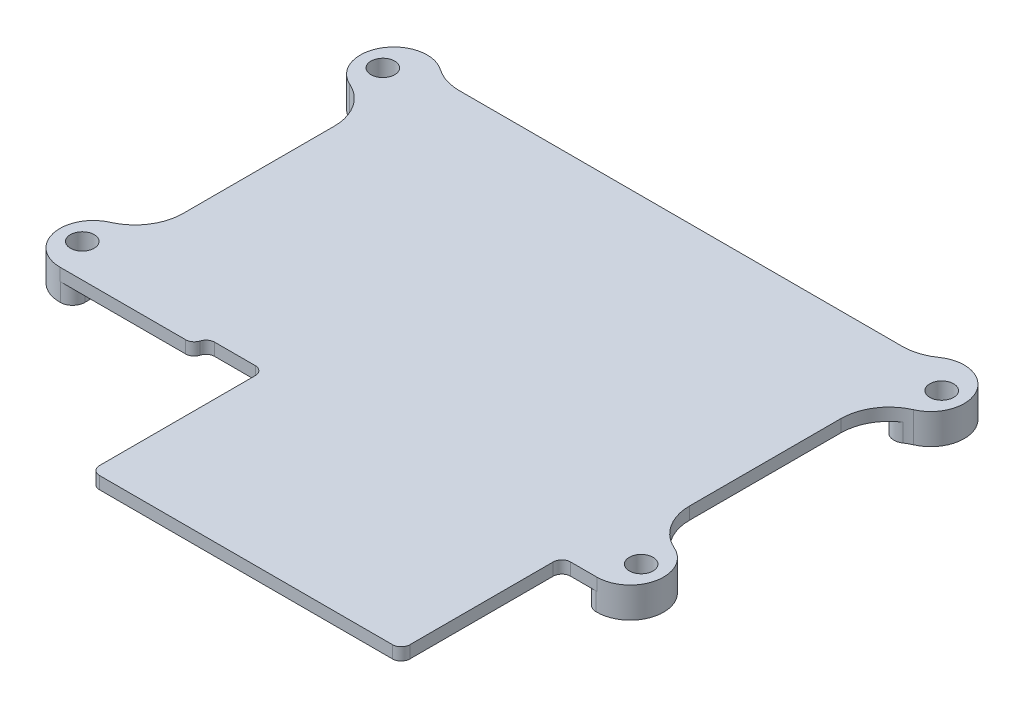
SolidWorks part; units mm, degrees
ref_plane "Front Plane" through (0, 0, 0) normal (0, 0, 1) x (1, 0, 0)
ref_plane "Top Plane" through (0, 0, 0) normal (0, 1, 0) x (1, 0, 0)
ref_plane "Right Plane" through (0, 0, 0) normal (1, 0, 0) x (0, 0, -1)
sketch "Sketch1" plane through (0, 0, 0) normal (0, 1, 0) x (1, 0, 0)
  line L0 (26.2382, 18.5875) -> (26.2382, 12.2481)
  line L1 (-27.5463, -15.4178) -> (27.5463, -15.4178) construction
  line L2 (-27.5463, -15.4178) -> (-27.5463, 15.4178) construction
  line L3 (-27.5463, 15.4178) -> (27.5463, 15.4178) construction
  line L4 (27.5463, -15.4178) -> (27.5463, 15.4178) construction
  line L5 (-27.5463, -15.4178) -> (27.5463, 15.4178) construction
  line L6 (-27.5463, 15.4178) -> (27.5463, -15.4178) construction
  line L7 (-28.6703, -15.4178) -> (28.6702, -15.4178) construction
  line L8 (-28.6703, -15.4178) -> (-28.6703, 15.4178) construction
  line L9 (-28.6703, 15.4178) -> (28.6702, 15.4178) construction
  line L10 (28.6702, -15.4178) -> (28.6702, 15.4178) construction
  line L11 (-28.6703, -15.4178) -> (28.6702, 15.4178) construction
  line L12 (-28.6703, 15.4178) -> (28.6702, -15.4178) construction
  line L13 (-26.2382, 18.5875) -> (-26.2382, 12.2481)
  line L14 (26.2382, -12.2481) -> (26.2382, -18.5875)
  line L15 (-26.2382, -12.2481) -> (-26.2382, -18.5875)
  arc A0 (26.2382, 12.2481) -> (26.2382, 18.5875) centre (27.5463, 15.4178) ccw
  arc A1 (-26.2382, 18.5875) -> (-26.2382, 12.2481) centre (-27.5463, 15.4178) ccw
  arc A2 (-26.2382, -12.2481) -> (-26.2382, -18.5875) centre (-27.5463, -15.4178) ccw
  circle A4 centre (28.6702, 15.4178) radius 1.2192
  circle A5 centre (-28.6703, 15.4178) radius 1.2192
  circle A6 centre (-28.6703, -15.4178) radius 1.2192
  circle A7 centre (28.6702, -15.4178) radius 1.2192
  arc A8 (26.2382, -18.5875) -> (26.2382, -12.2481) centre (27.5463, -15.4178) ccw
  point P0 (0, 0)
  point P10 (0, 0)
  dimension "D1" = 6.858
  dimension "D2" = 2.4384
  dimension "D3" = 57.3405
  dimension "D4" = 55.0926
  dimension "D5" = 30.8356
  dimension "D6" = 2.432
  dimension "D7" = 2.432
extrude "Boss-Extrude1" add sketch "Sketch1" along normal blind 3.1242
sketch "Sketch2" plane through (0, 3.1242, 0) normal (0, 1, 0) x (1, 0, 0)
  line L0 (-24.6952, 17.3228) -> (24.6952, 17.3228)
  line L2 (-25.9842, 12.3653) -> (-25.9842, -12.3653)
  line L3 (25.9842, 12.3653) -> (25.9842, -12.3653)
  line L4 (27.5463, -18.8468) -> (-27.5463, -18.8468)
  line L6 (-26.2382, 12.2481) -> (-26.2382, 18.5875) construction
  line L7 (26.2382, 18.5875) -> (26.2382, 12.2481) construction
  arc A0 (-26.2382, 18.5875) -> (-26.2382, 12.2481) centre (-27.5463, 15.4178) ccw construction
  arc A1 (-24.6952, 17.3228) -> (-25.9842, 12.3653) centre (-27.5463, 15.4178) ccw
  arc A2 (26.2382, 12.2481) -> (26.2382, 18.5875) centre (27.5463, 15.4178) ccw construction
  arc A3 (25.9842, 12.3653) -> (24.6952, 17.3228) centre (27.5463, 15.4178) ccw
  arc A4 (26.2382, -18.5875) -> (26.2382, -12.2481) centre (27.5463, -15.4178) ccw construction
  arc A5 (27.5463, -18.8468) -> (25.9842, -12.3653) centre (27.5463, -15.4178) ccw
  arc A6 (-26.2382, -12.2481) -> (-26.2382, -18.5875) centre (-27.5463, -15.4178) ccw construction
  arc A7 (-25.9842, -12.3653) -> (-27.5463, -18.8468) centre (-27.5463, -15.4178) ccw
  circle A8 centre (28.6702, -15.4178) radius 1.2192 construction
  circle A9 centre (28.6702, -15.4178) radius 1.2192
  circle A10 centre (28.6702, 15.4178) radius 1.2192 construction
  circle A11 centre (28.6702, 15.4178) radius 1.2192
  circle A12 centre (-28.6703, 15.4178) radius 1.2192 construction
  circle A13 centre (-28.6703, 15.4178) radius 1.2192
  circle A14 centre (-28.6703, -15.4178) radius 1.2192 construction
  circle A15 centre (-28.6703, -15.4178) radius 1.2192
  dimension "D1" = 1.905
  dimension "D2" = 0.254
  dimension "D3" = 0.254
extrude "Boss-Extrude2" add sketch "Sketch2" against normal blind 1.27
sketch "Sketch4" plane through (0, 3.1242, 0) normal (0, 1, 0) x (1, 0, 0)
  line L0 (-27.5463, -18.8468) -> (27.5463, -18.8468) construction
  line L1 (-13.8176, -18.8468) -> (-7.874, -18.8468)
  line L2 (-13.8176, -18.8468) -> (-13.8176, -17.5768)
  line L3 (-13.8176, -17.5768) -> (-7.874, -17.5768)
  line L4 (-7.874, -18.8468) -> (-7.874, -17.5768)
  point P6 (-10.8458, -17.5768)
  dimension "D1" = 10.8458
  dimension "D2" = 5.9436
  dimension "D3" = 1.27
extrude "Cut-Extrude1" cut sketch "Sketch4" against normal up to surface (1.27 mm away) up to face at (0, 1.8542, 0.1842)
fillet "Fillet1" radius 4.953 6 edges at (-25.9842, 2.4892, 12.3653) (25.9842, 2.4892, -12.3653) (24.6952, 2.4892, -17.3228) (25.9842, 2.4892, 12.3653) (-24.6952, 2.4892, -17.3228) (-25.9842, 2.4892, -12.3653)
sketch "Sketch6" plane through (0, 3.1242, 0) normal (0, 1, 0) x (1, 0, 0)
  line L1 (-22.4155, 4.5466) -> (-13.1445, 4.5466)
  line L2 (-22.4155, 4.5466) -> (-22.4155, 13.8176)
  line L3 (-22.4155, 13.8176) -> (-13.1445, 13.8176)
  line L4 (-13.1445, 4.5466) -> (-13.1445, 13.8176)
  line L5 (-22.4155, 4.5466) -> (-13.1445, 13.8176) construction
  line L6 (-22.4155, 13.8176) -> (-13.1445, 4.5466) construction
  point P0 (-17.78, 9.1821)
  dimension "D1" = 17.78
  dimension "D2" = 9.1821
  dimension "D3" = 9.271
  dimension "D4" = 9.271
sketch "Sketch7" plane through (0, 3.1242, 0) normal (0, 1, 0) x (1, 0, 0)
  line L0 (-7.874, -25.0444) -> (-7.874, -35.3314)
  line L1 (23.9649, -35.3314) -> (-8.2931, -35.3314) construction
  line L2 (23.9649, -35.3314) -> (23.9649, -25.0444)
  line L3 (23.9649, -25.0444) -> (-8.2931, -25.0444) construction
  line L4 (-8.2931, -35.3314) -> (-8.2931, -25.0444) construction
  line L5 (-7.874, -18.8468) -> (-7.874, -17.5768) construction
  line L6 (-7.874, -25.0444) -> (23.9649, -25.0444) construction
  line L7 (23.9649, -35.3314) -> (-7.874, -35.3314)
  line L8 (23.9649, -25.0444) -> (23.9649, -18.8468)
  line L9 (-7.874, -18.8468) -> (27.5463, -18.8468) construction
  line L10 (23.9649, -18.8468) -> (-7.874, -18.8468)
  line L11 (-7.874, -18.8468) -> (-7.874, -25.0444)
  point P4 (7.8359, -25.0444)
  point P6 (-8.2931, -30.1879)
  dimension "D1" = 32.258
  dimension "D2" = 7.8359
  dimension "D3" = 30.1879
  dimension "D4" = 10.287
extrude "Boss-Extrude3" add sketch "Sketch7" against normal up to surface (1.27 mm away) up to face at (-1.972, 1.8542, 1.8173)
fillet "Fillet2" radius 0.889 3 edges at (-13.8176, 2.4892, 17.5768) (-7.874, 2.4892, 17.5768) (23.9649, 2.4892, 18.8468)
fillet "Fillet3" radius 0.889 3 edges at (-13.8176, 2.4892, 18.8468) (23.9649, 2.4892, 35.3314) (-7.874, 2.4892, 35.3314)
fillet "Fillet5" radius 1.27 8 edges at (26.2382, 0.9271, 9.3181) (26.2382, 0.9271, -9.3181) (-26.2382, 0.9271, -9.3181) (-26.2382, 0.9271, 9.3181) (26.2382, 0.9271, -18.5875) (-26.2382, 0.9271, -18.5875) (-26.2382, 0.9271, 18.5875) (26.2382, 0.9271, 18.5875)
equation "\"D3@Sketch2\"=\"D2@Sketch2\""
